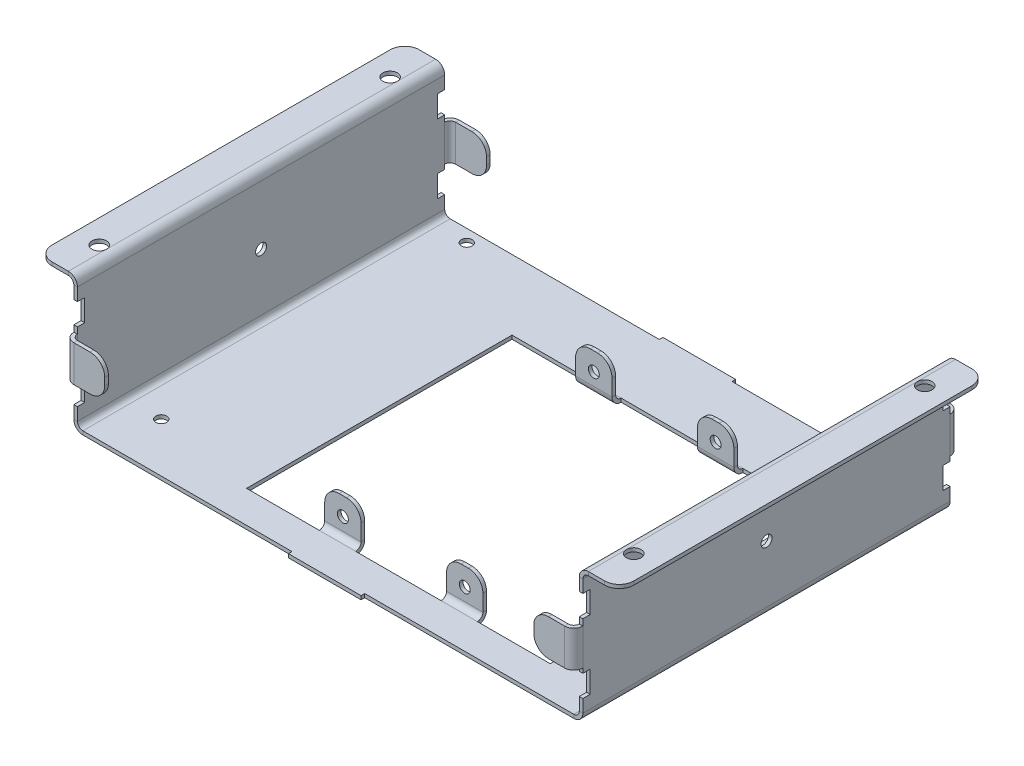
SolidWorks part; units mm, degrees
note: The reader was unsure of these and kept them because the rebuilt part matched: flange length of "Edge-Flange1", "Edge-Flange2", "Edge-Flange3", "Edge-Flange5", "Edge-Flange6".
material "Galvanized Steel"
ref_plane "Front Plane" through (0, 0, 0) normal (0, 0, 1) x (1, 0, 0)
ref_plane "Top Plane" through (0, 0, 0) normal (0, 1, 0) x (1, 0, 0)
ref_plane "Right Plane" through (0, 0, 0) normal (1, 0, 0) x (0, 0, -1)
sketch "Sketch2" plane through (0, 0, 0) normal (0, 1, 0) x (1, 0, 0)
  line L0 (-67.5, -45) -> (-10, -45)
  line L1 (10, 56) -> (67.5, 56)
  line L2 (67.5, -45) -> (67.5, 56)
  line L3 (10, -45) -> (67.5, -45)
  line L4 (-67.5, -45) -> (-67.5, 56)
  line L5 (10, 56) -> (10, 57)
  line L6 (10, 57) -> (-10, 57)
  line L7 (-31.3, 36.8) -> (52.2, 36.8)
  line L8 (-31.3, 36.8) -> (-31.3, -36.2)
  line L9 (-31.3, -36.2) -> (52.2, -36.2)
  line L10 (52.2, 36.8) -> (52.2, -36.2)
  line L11 (-10, 56) -> (-10, 57)
  line L13 (-10, -45) -> (-10, -46)
  line L14 (-10, -46) -> (10, -46)
  line L15 (-67.5, 56) -> (-10, 56)
  line L16 (10, -45) -> (10, -46)
  point P0 (0, 0)
  point P6 (-10, 56.5)
  point P19 (-10, -45.5)
  dimension "D1" = 101
  dimension "D2" = 45
  dimension "D3" = 135
  dimension "D4" = 83.5
  dimension "D5" = 36.2
  dimension "D6" = 73
  dimension "D7" = 67.5
  dimension "D8" = 8.8
  dimension "D9" = 57.5
  dimension "D10" = 20
  dimension "D11" = 1
  dimension "D12" = 1
  dimension "D13" = 20
  dimension "D14" = 57.5
base flange "Base-Flange1" sketch "Sketch2" thickness 1 reverse thickness direction no parameters "D1"=1
edge flange "Edge-Flange1" sketch "Sketch11" flange profiles "Sketch11", "Sketch12" flange angle 90 flange length 10 flange position bend outside bend radius 1.5 thickness 1 relief rectangular parameters "D6"=10, "D8"=1
sketch "Sketch11" plane through (0, 0, 36.2) normal (0, 0, -1) x (-1, 0, 0)
  line L2 (-32.2, 0) -> (-32.2, 6)
  line L3 (-28.2, 10) -> (-26.2, 10)
  line L4 (-22.2, 6) -> (-22.2, 0)
  line L5 (31.3, 0) -> (-52.2, 0) construction
  line L6 (-22.2, 0) -> (-32.2, 0)
  arc A0 (-32.2, 6) -> (-28.2, 10) centre (-28.2, 6) cw
  arc A1 (-26.2, 10) -> (-22.2, 6) centre (-26.2, 6) cw
  point P9 (-32.2, 10)
  point P12 (-22.2, 10)
  dimension "D4" = 4
  dimension "D1" = 20
  dimension "D2" = 10
  dimension "D3" = 10
sketch "Sketch12" plane through (0, 0, -36.8) normal (0, 0, 1) x (1, 0, 0)
  line L0 (52.2, 0) -> (-31.3, 0) construction
  line L1 (32.2, 0) -> (22.2, 0)
  line L2 (22.2, 0) -> (22.2, 6)
  line L3 (26.2, 10) -> (28.2, 10)
  line L4 (32.2, 6) -> (32.2, 0)
  arc A0 (22.2, 6) -> (26.2, 10) centre (26.2, 6) cw
  arc A1 (28.2, 10) -> (32.2, 6) centre (28.2, 6) cw
  point P9 (22.2, 10)
  point P12 (32.2, 10)
  dimension "D4" = 4
  dimension "D1" = 20
  dimension "D2" = 10
  dimension "D3" = 10
bend "EdgeBend1" bend radius 1.5 bend angle 90 parameters "D5"=1
bend "EdgeBend2" bend radius 1.5 bend angle 90 parameters "D5"=2
edge flange "Edge-Flange2" sketch "Sketch17" flange profiles "Sketch17", "Sketch18" flange angle 90 flange length 10 flange position bend outside bend radius 1.5 thickness 1 relief rectangular parameters "D6"=10, "D8"=1
sketch "Sketch17" plane through (0, 0, -36.8) normal (0, 0, 1) x (1, 0, 0)
  line L2 (-11.3, 0) -> (-11.3, 6)
  line L3 (-7.3, 10) -> (-5.3, 10)
  line L4 (-1.3, 6) -> (-1.3, 0)
  line L5 (22.2, 0) -> (-31.3, 0) construction
  line L6 (-1.3, 0) -> (-11.3, 0)
  arc A0 (-5.3, 10) -> (-1.3, 6) centre (-5.3, 6) cw
  arc A1 (-11.3, 6) -> (-7.3, 10) centre (-7.3, 6) cw
  point P9 (-1.3, 10)
  point P12 (-11.3, 10)
  dimension "D4" = 4
  dimension "D1" = 20
  dimension "D2" = 10
  dimension "D3" = 10
sketch "Sketch18" plane through (0, 0, 36.2) normal (0, 0, -1) x (-1, 0, 0)
  line L0 (31.3, 0) -> (-22.2, 0) construction
  line L1 (11.3, 0) -> (1.3, 0)
  line L2 (1.3, 0) -> (1.3, 6)
  line L3 (5.3, 10) -> (7.3, 10)
  line L4 (11.3, 6) -> (11.3, 0)
  arc A0 (1.3, 6) -> (5.3, 10) centre (5.3, 6) cw
  arc A1 (7.3, 10) -> (11.3, 6) centre (7.3, 6) cw
  point P9 (1.3, 10)
  point P12 (11.3, 10)
  dimension "D4" = 4
  dimension "D1" = 20
  dimension "D2" = 10
  dimension "D3" = 10
bend "EdgeBend3" bend radius 1.5 bend angle 90 parameters "D5"=3
bend "EdgeBend4" bend radius 1.5 bend angle 90 parameters "D5"=4
edge flange "Edge-Flange3" sketch "Sketch23" flange profiles "Sketch23", "Sketch24" flange angle 90 flange length 33.5 flange position bend outside bend radius 1.5 thickness 1 relief rectangular parameters "D6"=10, "D8"=1
sketch "Sketch23" plane through (-67.5, 0, 0) normal (-1, 0, 0) x (0, 0, 1)
  line L2 (-56, 0) -> (-56, 33.5)
  line L3 (-56, 33.5) -> (45, 33.5)
  line L4 (45, 33.5) -> (45, 0)
  line L5 (-56, 0) -> (45, 0) construction
  line L6 (-56, 0) -> (45, 0)
  dimension "D1" = 33.5
sketch "Sketch24" plane through (67.5, 0, 0) normal (1, 0, 0) x (0, 0, -1)
  line L0 (-45, 0) -> (56, 0) construction
  line L1 (-45, 0) -> (56, 0)
  line L2 (-45, 0) -> (-45, 33.5)
  line L3 (-45, 33.5) -> (56, 33.5)
  line L4 (56, 33.5) -> (56, 0)
  dimension "D1" = 33.5
bend "EdgeBend5" bend radius 1.5 bend angle 90 parameters "D5"=5
bend "EdgeBend6" bend radius 1.5 bend angle 90 parameters "D5"=6
edge flange "Edge-Flange5" sketch "Sketch32" flange profiles "Sketch32", "Sketch34", "Sketch36", "Sketch38" flange angle 90 flange length 10 flange position bend outside bend radius 1.5 thickness 1 relief rectangular parameters "D6"=10, "D8"=1
sketch "Sketch32" plane through (69, 0, 45) normal (0, 0, 1) x (0, 1, 0)
  line L0 (33.5, 0) -> (1.5, 0) construction
  line L1 (22.25, 0) -> (12.25, 0)
  line L2 (12.25, 0) -> (12.25, 6)
  line L3 (16.25, 10) -> (18.25, 10)
  line L4 (22.25, 6) -> (22.25, 0)
  line L5 (-1, 136.5) -> (-1, 79) construction
  arc A0 (18.25, 10) -> (22.25, 6) centre (18.25, 6) cw
  arc A1 (12.25, 6) -> (16.25, 10) centre (16.25, 6) cw
  point P10 (22.25, 10)
  point P13 (12.25, 10)
  dimension "D4" = 4
  dimension "D1" = 13.25
  dimension "D2" = 10
  dimension "D3" = 10
sketch "Sketch34" plane through (69, 0, -56) normal (0, 0, -1) x (0, -1, 0)
  line L0 (-1.5, 0) -> (-33.5, 0) construction
  line L1 (-12.25, 0) -> (-22.25, 0)
  line L2 (-22.25, 0) -> (-22.25, 6)
  line L3 (-18.25, 10) -> (-16.25, 10)
  line L4 (-12.25, 6) -> (-12.25, 0)
  line L7 (1, 79) -> (1, 136.5) construction
  arc A0 (-22.25, 6) -> (-18.25, 10) centre (-18.25, 6) cw
  arc A1 (-16.25, 10) -> (-12.25, 6) centre (-16.25, 6) cw
  point P9 (-22.25, 10)
  point P12 (-12.25, 10)
  dimension "D4" = 4
  dimension "D1" = 13.25
  dimension "D2" = 10
  dimension "D3" = 10
sketch "Sketch36" plane through (-69, 0, 45) normal (0, 0, 1) x (0, -1, 0)
  line L0 (-1.5, 0) -> (-33.5, 0) construction
  line L1 (-12.25, 0) -> (-22.25, 0)
  line L2 (-22.25, 0) -> (-22.25, 6)
  line L3 (-18.25, 10) -> (-16.25, 10)
  line L4 (-12.25, 6) -> (-12.25, 0)
  line L5 (1, 1.5) -> (1, 59) construction
  arc A0 (-16.25, 10) -> (-12.25, 6) centre (-16.25, 6) cw
  arc A1 (-22.25, 6) -> (-18.25, 10) centre (-18.25, 6) cw
  point P10 (-12.25, 10)
  point P13 (-22.25, 10)
  dimension "D4" = 4
  dimension "D1" = 13.25
  dimension "D2" = 10
  dimension "D3" = 10
sketch "Sketch38" plane through (-69, 0, -56) normal (0, 0, -1) x (0, 1, 0)
  line L0 (33.5, 0) -> (1.5, 0) construction
  line L1 (22.25, 0) -> (12.25, 0)
  line L2 (12.25, 0) -> (12.25, 6)
  line L3 (16.25, 10) -> (18.25, 10)
  line L4 (22.25, 6) -> (22.25, 0)
  line L5 (-1, 59) -> (-1, 1.5) construction
  arc A0 (18.25, 10) -> (22.25, 6) centre (18.25, 6) cw
  arc A1 (12.25, 6) -> (16.25, 10) centre (16.25, 6) cw
  point P10 (22.25, 10)
  point P13 (12.25, 10)
  dimension "D4" = 4
  dimension "D1" = 13.25
  dimension "D2" = 10
  dimension "D3" = 10
bend "EdgeBend9" bend radius 1.5 bend angle 90 parameters "D5"=7
bend "EdgeBend10" bend radius 1.5 bend angle 90 parameters "D5"=9
bend "EdgeBend11" bend radius 1.5 bend angle 90 parameters "D5"=10
bend "EdgeBend12" bend radius 1.5 bend angle 90 parameters "D5"=11
edge flange "Edge-Flange6" sketch "Sketch43" flange profiles "Sketch43", "Sketch44" flange angle 90 flange length 10 flange position bend outside bend radius 1.5 thickness 1 relief rectangular parameters "D6"=10, "D8"=1
sketch "Sketch43" plane through (70, 33.5, 0) normal (0, -1, 0) x (0, 0, -1)
  line L2 (-45, 0) -> (-45, 6)
  line L3 (-41, 10) -> (52, 10)
  line L4 (56, 6) -> (56, 0)
  line L6 (56, 0) -> (-45, 0) construction
  line L7 (56, 0) -> (-45, 0)
  arc A0 (-45, 6) -> (-41, 10) centre (-41, 6) cw
  arc A1 (52, 10) -> (56, 6) centre (52, 6) cw
  dimension "D1" = 4
sketch "Sketch44" plane through (-70, 33.5, 0) normal (0, -1, 0) x (0, 0, 1)
  line L0 (45, 0) -> (-56, 0) construction
  line L1 (45, 0) -> (-56, 0)
  line L2 (45, 0) -> (45, 6)
  line L3 (41, 10) -> (-52, 10)
  line L4 (-56, 6) -> (-56, 0)
  arc A0 (-52, 10) -> (-56, 6) centre (-52, 6) ccw
  arc A1 (45, 6) -> (41, 10) centre (41, 6) ccw
  dimension "D1" = 4
bend "EdgeBend13" bend radius 1.5 bend angle 90 parameters "D5"=12
bend "EdgeBend14" bend radius 1.5 bend angle 90 parameters "D5"=13
sketch "Sketch45" plane through (0, 36, 0) normal (0, 1, 0) x (1, 0, 0)
  line L0 (-80, 5.5) -> (-69, 5.5) construction
  line L1 (-80, -41) -> (-80, 52) construction
  line L2 (-69, 56) -> (-69, -45) construction
  line L3 (69, 5.5) -> (80, 5.5) construction
  line L4 (69, -45) -> (69, 56) construction
  line L5 (80, 52) -> (80, -41) construction
  point P6 (-73.5, 45.5)
  point P7 (-73.5, -34.5)
  point P14 (73.5, 45.5)
  point P15 (73.5, -34.5)
  dimension "D1" = 40
  dimension "D2" = 40
  dimension "D3" = 40
  dimension "D4" = 40
hole_wizard "Ø4.0mm Dowel Hole1" positions "Sketch46" profile "Sketch48" hole size "Ø4.0" standard "ANSI Metric" end condition up to next
sketch "Sketch46" plane through (0, 36, 0) normal (0, 1, 0) x (1, 0, 0)
  point P0 (-73.5, 45.5)
  point P3 (-73.5, -34.5)
  point P6 (73.5, -34.5)
  point P9 (73.5, 45.5)
sketch "Sketch48" plane through (-73.5, 36, -45.5) normal (1, 0, 0) x (0, 0, 1)
  line L0 (0, 0) -> (0, 1)
  line L1 (0, 1) -> (2, 1)
  line L2 (2, 1) -> (2, 0)
  line L5 (2, 0) -> (0, 0)
  line L11 (0, -6.35) -> (0, 107.95) construction
  dimension "Thru Hole Dia." = 4
  dimension "Thru Hole Depth" = 1
sketch "Sketch50" plane through (-70, 0, 0) normal (-1, 0, 0) x (0, 0, 1)
  line L0 (-56, 33.5) -> (-56, 22.25) construction
  line L1 (-56, 30) -> (-54, 30)
  line L2 (-56, 30) -> (-56, 24)
  line L3 (-56, 24) -> (-54, 24)
  line L4 (-54, 30) -> (-54, 24)
  line L6 (-56, 36) -> (-45.5, 36) construction
  line L7 (-56, 12.25) -> (-56, 1.5) construction
  line L8 (-56, 11) -> (-54, 11)
  line L9 (-56, 11) -> (-56, 5)
  line L10 (-56, 5) -> (-54, 5)
  line L11 (-54, 11) -> (-54, 5)
  line L12 (-56, -1) -> (45, -1) construction
  line L13 (-5.5, 33.5) -> (-5.5, 1.5) construction
  line L14 (45, 33.5) -> (-56, 33.5) construction
  line L15 (45, 1.5) -> (-56, 1.5) construction
  line L16 (43, 11) -> (43, 5)
  line L17 (45, 5) -> (43, 5)
  line L18 (45, 11) -> (45, 5)
  line L19 (45, 11) -> (43, 11)
  line L20 (43, 30) -> (43, 24)
  line L21 (45, 24) -> (43, 24)
  line L22 (45, 30) -> (45, 24)
  line L23 (45, 30) -> (43, 30)
  point P6 (-55, 30)
  dimension "D1" = 2
  dimension "D2" = 6
  dimension "D3" = 6
  dimension "D4" = 2
  dimension "D5" = 6
  dimension "D6" = 6
extrude "Cut-Extrude1" cut sketch "Sketch50" against normal blind 143 normal cut yes
unfold "Unfold1" [suppressed]
sketch "Sketch45-2" [suppressed] plane through (34.427, 0, 0) normal (0, 1, 0) x (1, 0, 0)
  line L0 (-79, 5.5) -> (-68, 5.5) construction
  line L3 (68, 5.5) -> (79, 5.5) construction
  point P6 (-73.5, 45.5)
  point P7 (-73.5, -34.5)
  point P14 (73.5, 45.5)
  point P15 (73.5, -34.5)
  dimension "D1" = 40
  dimension "D2" = 40
  dimension "D3" = 40
  dimension "D4" = 40
sketch "Sketch50-1" plane through (-68.5708, -1, 0) normal (0, -1, 0) x (0, 0, 1)
  line L1 (-56, 29.5) -> (-54, 29.5)
  line L2 (-56, 29.5) -> (-56, 23.5)
  line L3 (-56, 23.5) -> (-54, 23.5)
  line L4 (-54, 29.5) -> (-54, 23.5)
  line L8 (-56, 11) -> (-54, 11)
  line L9 (-56, 11) -> (-56, 5)
  line L10 (-56, 5) -> (-54, 5)
  line L11 (-54, 11) -> (-54, 5)
  line L12 (-56, -1.0708) -> (45, -1.0708) construction
  line L13 (-5.5, 33.5) -> (-5.5, 0.5) construction
  line L16 (43, 11) -> (43, 5)
  line L17 (45, 5) -> (43, 5)
  line L18 (45, 11) -> (45, 5)
  line L19 (45, 11) -> (43, 11)
  line L20 (43, 29.5) -> (43, 23.5)
  line L21 (45, 23.5) -> (43, 23.5)
  line L22 (45, 29.5) -> (45, 23.5)
  line L23 (45, 29.5) -> (43, 29.5)
  dimension "D1" = 2
  dimension "D2" = 6
  dimension "D4" = 2
  dimension "D5" = 6
  dimension "D6" = 6.0708
sketch "Sketch51" plane through (70, 0, 0) normal (1, 0, 0) x (0, 0, -1)
  line L0 (-31.4511, 24.5488) -> (-31.4511, 22.9482) construction
  line L1 (55.5489, 22.9482) -> (-34.4511, 22.9482) construction
  line L3 (52.5489, 24.5488) -> (52.5498, 22.935) construction
  point P0 (-31.4511, 24.5488)
sketch "Sketch53" plane through (0, 0, 0) normal (0, 1, 0) x (1, 0, 0)
  point P0 (-59.4974, 52.5489)
  point P1 (59.5026, 52.5489)
  point P3 (-59.4974, -31.4511)
  point P5 (59.5026, -31.4511)
hole_wizard "Ø3.0mm Dowel Hole1" positions "Sketch56" profile "Sketch57" hole size "Ø3.0" standard "ANSI Metric" end condition up to next
sketch "Sketch56" plane through (0, 0, 0) normal (0, 1, 0) x (1, 0, 0)
  point P0 (-59.4974, 52.5489)
  point P3 (59.5026, 52.5489)
  point P6 (-59.4974, -31.4511)
  point P9 (59.5026, -31.4511)
sketch "Sketch57" plane through (-59.4974, 0, -52.5489) normal (1, 0, 0) x (0, 0, 1)
  line L0 (0, 0) -> (0, 1)
  line L1 (0, 1) -> (1.5, 1)
  line L2 (1.5, 1) -> (1.5, 0)
  line L5 (1.5, 0) -> (0, 0)
  line L11 (0, -6.35) -> (0, 107.95) construction
  dimension "Thru Hole Dia." = 3
  dimension "Thru Hole Depth" = 1
sketch "Sketch58" plane through (0, 0, 34.7) normal (0, 0, 1) x (1, 0, 0)
  line L1 (-1.3, 6) -> (-1.3, 1.5) construction
  line L2 (-67.5, 0) -> (-10, 0) construction
  line L3 (10, 0) -> (67.5, 0) construction
  line L4 (32.2, 6) -> (32.2, 1.5) construction
  point P0 (-6.3, 5)
  point P6 (27.2, 5)
  point P11 (32.2, 3.75)
  dimension "D1" = 5
  dimension "D2" = 5
  dimension "D3" = 5
  dimension "D4" = 5
sketch "Sketch59" plane through (0, 0, -35.3) normal (0, 0, -1) x (-1, 0, 0)
  point P0 (-27.2, 5)
  point P1 (6.3, 5)
hole_wizard "Ø3.0mm Dowel Hole2" positions "Sketch60" profile "Sketch61" hole size "Ø3.0" standard "ANSI Metric" end condition up to next
sketch "Sketch60" plane through (0, 0, -35.3) normal (0, 0, -1) x (-1, 0, 0)
  point P0 (-27.2, 5)
  point P3 (6.3, 5)
  point P6 (6.3, 5)
sketch "Sketch61" plane through (27.2, 5, -35.3) normal (1, 0, 0) x (0, 1, 0)
  line L0 (0, 0) -> (0, 1)
  line L1 (0, 1) -> (1.5, 1)
  line L2 (1.5, 1) -> (1.5, 0)
  line L5 (1.5, 0) -> (0, 0)
  line L11 (0, -6.35) -> (0, 107.95) construction
  dimension "Thru Hole Dia." = 3
  dimension "Thru Hole Depth" = 1
hole_wizard "Ø3.0mm Dowel Hole3" positions "Sketch64" profile "Sketch65" hole size "Ø3.0" standard "ANSI Metric" end condition up to next
sketch "Sketch64" plane through (0, 0, 34.7) normal (0, 0, 1) x (1, 0, 0)
  point P0 (-6.3, 5)
  point P3 (27.2, 5)
sketch "Sketch65" plane through (-6.3, 5, 34.7) normal (1, 0, 0) x (0, -1, 0)
  line L0 (0, 0) -> (0, 1)
  line L1 (0, 1) -> (1.5, 1)
  line L2 (1.5, 1) -> (1.5, 0)
  line L5 (1.5, 0) -> (0, 0)
  line L11 (0, -6.35) -> (0, 107.95) construction
  dimension "Thru Hole Dia." = 3
  dimension "Thru Hole Depth" = 1
ref_plane "Plane1" through (0, 0, 0) normal (-1, 0, 0) x (0, 0, 1)
sketch "Sketch66" plane through (70, 0, 0) normal (1, 0, 0) x (0, 0, -1)
  line L0 (-45, 17.25) -> (56, 17.25) construction
  line L1 (-45, 22.25) -> (-45, 12.25) construction
  line L2 (56, 12.25) -> (56, 22.25) construction
  point P6 (5.5, 17.25)
hole_wizard "Ø3.0 (3) Diameter Hole1" positions "Sketch67" profile "Sketch68" hole size "Ø3.0" standard "ANSI Metric" end condition up to next
sketch "Sketch67" plane through (70, 0, 0) normal (1, 0, 0) x (0, 0, -1)
  point P0 (5.5, 17.25)
sketch "Sketch68" plane through (70, 17.25, -5.5) normal (0, 1, 0) x (0, 0, -1)
  line L0 (0, 0) -> (0, 1)
  line L1 (0, 1) -> (1.5, 1)
  line L2 (1.5, 1) -> (1.5, 0)
  line L5 (1.5, 0) -> (0, 0)
  line L11 (0, -6.35) -> (0, 107.95) construction
  dimension "Thru Hole Dia." = 3
  dimension "Thru Hole Depth" = 1
sketch "Sketch70" plane through (-70, 0, 0) normal (-1, 0, 0) x (0, 0, 1)
  line L0 (-56, 17.25) -> (45, 17.25) construction
  line L1 (-56, 22.25) -> (-56, 12.25) construction
  line L2 (45, 12.25) -> (45, 22.25) construction
  point P6 (-5.5, 17.25)
hole_wizard "Ø3.0mm Dowel Hole4" positions "Sketch71" profile "Sketch72" hole size "Ø3.0" standard "ANSI Metric" end condition up to next
sketch "Sketch71" plane through (-70, 0, 0) normal (-1, 0, 0) x (0, 0, 1)
  point P0 (-5.5, 17.25)
sketch "Sketch72" plane through (-70, 17.25, -5.5) normal (0, 1, 0) x (0, 0, 1)
  line L0 (0, 0) -> (0, 1)
  line L1 (0, 1) -> (1.5, 1)
  line L2 (1.5, 1) -> (1.5, 0)
  line L5 (1.5, 0) -> (0, 0)
  line L11 (0, -6.35) -> (0, 107.95) construction
  dimension "Thru Hole Dia." = 3
  dimension "Thru Hole Depth" = 1
sketch "Bend-Lines1" [suppressed] plane through (0, 0, 0) normal (0, 1, 0) x (1, 0, 0)
sketch "Bounding-Box1" [suppressed] plane through (0, 0, 0) normal (0, 1, 0) x (1, 0, 0)
sheet metal parameters "Sheet-Metal1" thickness 1 parameters "D1"=1
flat pattern "Flat-Pattern1"
sketch "Bend-Lines2" plane through (0, 0, 0) normal (0, 1, 0) x (1, 0, 0)
sketch3d "Bounding-Box2" [suppressed]
  line L0 (67.5, -54, 0) -> (-67.5, -54, 0) construction
  line L1 (67.5, 54, 0) -> (-67.5, 54, 0) construction
  line L2 (67.5, -54, 0) -> (67.5, 54, 0) construction
  line L3 (-67.5, -54, 0) -> (-67.5, 54, 0) construction
sheet metal parameters "Sheet-Metal2" thickness 1 parameters "D1"=1
flat pattern "Flat-Pattern1"
sketch "Bend-Lines2" plane through (0, 0, 0) normal (0, 1, 0) x (1, 0, 0)
  line L0 (22.2, 35.0146) -> (32.2, 35.0146) construction
  line L1 (32.2, -35.4146) -> (22.2, -35.4146) construction
  line L2 (22.2, 35.0146) -> (32.2, 35.0146) construction
  line L3 (32.2, -35.4146) -> (22.2, -35.4146) construction
sketch3d "Bounding-Box2" [suppressed]
  line L0 (67.5, -45, 0) -> (-67.5, -45, 0) construction
  line L1 (67.5, 56, 0) -> (-67.5, 56, 0) construction
  line L2 (67.5, -45, 0) -> (67.5, 56, 0) construction
  line L3 (-67.5, -45, 0) -> (-67.5, 56, 0) construction
bend of the flat pattern "Flatten-<EdgeBend1>1"
bend of the flat pattern "Flatten-<EdgeBend2>1"
sheet metal parameters "Sheet-Metal3" thickness 1 parameters "D1"=1
flat pattern "Flat-Pattern1"
sketch "Bend-Lines2" plane through (0, 0, 0) normal (0, 1, 0) x (1, 0, 0)
  line L0 (22.2, 35.0146) -> (32.2, 35.0146) construction
  line L1 (32.2, -35.4146) -> (22.2, -35.4146) construction
  line L2 (22.2, 35.0146) -> (32.2, 35.0146) construction
  line L3 (32.2, -35.4146) -> (22.2, -35.4146) construction
  line L4 (22.2, -35.4146) -> (-11.3, -35.4146) construction
  line L5 (-11.3, 35.0146) -> (22.2, 35.0146) construction
  line L6 (22.2, -35.4146) -> (-11.3, -35.4146) construction
  line L7 (-11.3, 35.0146) -> (22.2, 35.0146) construction
sketch3d "Bounding-Box2" [suppressed]
  line L0 (67.5, -45, 0) -> (-67.5, -45, 0) construction
  line L1 (67.5, 56, 0) -> (-67.5, 56, 0) construction
  line L2 (67.5, -45, 0) -> (67.5, 56, 0) construction
  line L3 (-67.5, -45, 0) -> (-67.5, 56, 0) construction
bend of the flat pattern "Flatten-<EdgeBend1>1"
bend of the flat pattern "Flatten-<EdgeBend2>1"
bend of the flat pattern "Flatten-<EdgeBend3>1"
bend of the flat pattern "Flatten-<EdgeBend4>1"
sheet metal parameters "Sheet-Metal4" thickness 1 parameters "D1"=1
flat pattern "Flat-Pattern1"
sketch "Bend-Lines2" plane through (0, 0, 0) normal (0, 1, 0) x (1, 0, 0)
  line L0 (22.2, 35.0146) -> (32.2, 35.0146) construction
  line L1 (32.2, -35.4146) -> (22.2, -35.4146) construction
  line L2 (22.2, 35.0146) -> (32.2, 35.0146) construction
  line L3 (32.2, -35.4146) -> (22.2, -35.4146) construction
  line L4 (22.2, -35.4146) -> (-11.3, -35.4146) construction
  line L5 (-11.3, 35.0146) -> (22.2, 35.0146) construction
  line L6 (22.2, -35.4146) -> (-11.3, -35.4146) construction
  line L7 (-11.3, 35.0146) -> (22.2, 35.0146) construction
  line L8 (68.2854, -45) -> (68.2854, 56) construction
  line L9 (-68.2854, 56) -> (-68.2854, -45) construction
  line L10 (68.2854, -45) -> (68.2854, 56) construction
  line L11 (-68.2854, 56) -> (-68.2854, -45) construction
sketch3d "Bounding-Box2" [suppressed]
  line L0 (104.0708, -45, 0) -> (-104.0708, -45, 0) construction
  line L1 (104.0708, 56, 0) -> (-104.0708, 56, 0) construction
  line L2 (104.0708, -45, 0) -> (104.0708, 56, 0) construction
  line L3 (-104.0708, -45, 0) -> (-104.0708, 56, 0) construction
bend of the flat pattern "Flatten-<EdgeBend1>1"
bend of the flat pattern "Flatten-<EdgeBend2>1"
bend of the flat pattern "Flatten-<EdgeBend3>1"
bend of the flat pattern "Flatten-<EdgeBend4>1"
bend of the flat pattern "Flatten-<EdgeBend5>1"
bend of the flat pattern "Flatten-<EdgeBend6>1"
sheet metal parameters "Sheet-Metal6" thickness 1 parameters "D1"=1
flat pattern "Flat-Pattern1"
sketch "Bend-Lines2" plane through (0, 0, 0) normal (0, 1, 0) x (1, 0, 0)
  line L0 (22.2, 35.0146) -> (32.2, 35.0146) construction
  line L1 (32.2, -35.4146) -> (22.2, -35.4146) construction
  line L2 (22.2, 35.0146) -> (32.2, 35.0146) construction
  line L3 (32.2, -35.4146) -> (22.2, -35.4146) construction
  line L4 (22.2, -35.4146) -> (-11.3, -35.4146) construction
  line L5 (-11.3, 35.0146) -> (22.2, 35.0146) construction
  line L6 (22.2, -35.4146) -> (-11.3, -35.4146) construction
  line L7 (-11.3, 35.0146) -> (22.2, 35.0146) construction
  line L8 (68.2854, -45) -> (68.2854, 56) construction
  line L9 (-68.2854, 56) -> (-68.2854, -45) construction
  line L10 (68.2854, -45) -> (68.2854, 56) construction
  line L11 (-68.2854, 56) -> (-68.2854, -45) construction
  line L12 (80.8208, -46.1781) -> (90.8208, -46.1781) construction
  line L13 (80.8208, -46.1781) -> (90.8208, -46.1781) construction
  line L14 (-80.8208, 57.1781) -> (-90.8208, 57.1781) construction
  line L15 (-90.8208, -46.1781) -> (-80.8208, -46.1781) construction
  line L16 (90.8208, 57.1781) -> (80.8208, 57.1781) construction
  line L17 (-80.8208, 57.1781) -> (-90.8208, 57.1781) construction
  line L18 (-90.8208, -46.1781) -> (-80.8208, -46.1781) construction
  line L19 (90.8208, 57.1781) -> (80.8208, 57.1781) construction
sketch3d "Bounding-Box2" [suppressed]
  line L0 (-104.0708, -56.356, 0) -> (104.0708, -56.3562, 0) construction
  line L1 (-104.0707, 67.3562, 0) -> (104.0709, 67.356, 0) construction
  line L2 (-104.0708, -56.356, 0) -> (-104.0707, 67.3562, 0) construction
  line L3 (104.0708, -56.3562, 0) -> (104.0709, 67.356, 0) construction
bend of the flat pattern "Flatten-<EdgeBend1>1"
bend of the flat pattern "Flatten-<EdgeBend2>1"
bend of the flat pattern "Flatten-<EdgeBend3>1"
bend of the flat pattern "Flatten-<EdgeBend4>1"
bend of the flat pattern "Flatten-<EdgeBend5>1"
bend of the flat pattern "Flatten-<EdgeBend6>1"
bend of the flat pattern "Flatten-<EdgeBend9>1"
bend of the flat pattern "Flatten-<EdgeBend10>1"
bend of the flat pattern "Flatten-<EdgeBend11>1"
bend of the flat pattern "Flatten-<EdgeBend12>1"
sheet metal parameters "Sheet-Metal7" thickness 1 parameters "D1"=1
flat pattern "Flat-Pattern1"
sketch "Bend-Lines2" plane through (0, 0, 0) normal (0, 1, 0) x (1, 0, 0)
  line L0 (22.2, 35.0146) -> (32.2, 35.0146) construction
  line L1 (32.2, -35.4146) -> (22.2, -35.4146) construction
  line L2 (22.2, 35.0146) -> (32.2, 35.0146) construction
  line L3 (32.2, -35.4146) -> (22.2, -35.4146) construction
  line L4 (22.2, -35.4146) -> (-11.3, -35.4146) construction
  line L5 (-11.3, 35.0146) -> (22.2, 35.0146) construction
  line L6 (22.2, -35.4146) -> (-11.3, -35.4146) construction
  line L7 (-11.3, 35.0146) -> (22.2, 35.0146) construction
  line L8 (68.2854, -45) -> (68.2854, 56) construction
  line L9 (-68.2854, 56) -> (-68.2854, -45) construction
  line L10 (68.2854, -45) -> (68.2854, 56) construction
  line L11 (-68.2854, 56) -> (-68.2854, -45) construction
  line L12 (80.8208, -46.1781) -> (90.8208, -46.1781) construction
  line L13 (80.8208, -46.1781) -> (90.8208, -46.1781) construction
  line L14 (-80.8208, 57.1781) -> (-90.8208, 57.1781) construction
  line L15 (-90.8208, -46.1781) -> (-80.8208, -46.1781) construction
  line L16 (90.8208, 57.1781) -> (80.8208, 57.1781) construction
  line L17 (-80.8208, 57.1781) -> (-90.8208, 57.1781) construction
  line L18 (-90.8208, -46.1781) -> (-80.8208, -46.1781) construction
  line L19 (90.8208, 57.1781) -> (80.8208, 57.1781) construction
  line L20 (-105.2489, 56) -> (-105.2489, -45) construction
  line L21 (105.2489, -45) -> (105.2489, 56) construction
  line L22 (-105.2489, 56) -> (-105.2489, -45) construction
  line L23 (105.2489, -45) -> (105.2489, 56) construction
sketch3d "Bounding-Box2" [suppressed]
  line L0 (-115.427, -56.356, 0) -> (115.427, -56.3562, 0) construction
  line L1 (-115.4269, 67.3562, 0) -> (115.4271, 67.356, 0) construction
  line L2 (-115.427, -56.356, 0) -> (-115.4269, 67.3562, 0) construction
  line L3 (115.427, -56.3562, 0) -> (115.4271, 67.356, 0) construction
bend of the flat pattern "Flatten-<EdgeBend1>1"
bend of the flat pattern "Flatten-<EdgeBend2>1"
bend of the flat pattern "Flatten-<EdgeBend3>1"
bend of the flat pattern "Flatten-<EdgeBend4>1"
bend of the flat pattern "Flatten-<EdgeBend5>1"
bend of the flat pattern "Flatten-<EdgeBend6>1"
bend of the flat pattern "Flatten-<EdgeBend9>1"
bend of the flat pattern "Flatten-<EdgeBend10>1"
bend of the flat pattern "Flatten-<EdgeBend11>1"
bend of the flat pattern "Flatten-<EdgeBend12>1"
bend of the flat pattern "Flatten-<EdgeBend13>1"
bend of the flat pattern "Flatten-<EdgeBend14>1"
sheet metal parameters "Sheet-Metal8" thickness 1 parameters "D1"=1
flat pattern "Flat-Pattern1" [suppressed]
sketch "Bend-Lines2" plane through (0, 0, 0) normal (0, 1, 0) x (1, 0, 0)
  line L0 (22.2, 35.0146) -> (32.2, 35.0146) construction
  line L1 (32.2, -35.4146) -> (22.2, -35.4146) construction
  line L2 (22.2, 35.0146) -> (32.2, 35.0146) construction
  line L3 (32.2, -35.4146) -> (22.2, -35.4146) construction
  line L4 (22.2, -35.4146) -> (-11.3, -35.4146) construction
  line L5 (-11.3, 35.0146) -> (22.2, 35.0146) construction
  line L6 (22.2, -35.4146) -> (-11.3, -35.4146) construction
  line L7 (-11.3, 35.0146) -> (22.2, 35.0146) construction
  line L8 (68.2854, -45) -> (68.2854, 56) construction
  line L9 (-68.2854, 56) -> (-68.2854, -45) construction
  line L10 (68.2854, -45) -> (68.2854, 56) construction
  line L11 (-68.2854, 56) -> (-68.2854, -45) construction
  line L12 (80.8208, -46.1781) -> (90.8208, -46.1781) construction
  line L13 (80.8208, -46.1781) -> (90.8208, -46.1781) construction
  line L14 (-80.8208, 57.1781) -> (-90.8208, 57.1781) construction
  line L15 (-90.8208, -46.1781) -> (-80.8208, -46.1781) construction
  line L16 (90.8208, 57.1781) -> (80.8208, 57.1781) construction
  line L17 (-80.8208, 57.1781) -> (-90.8208, 57.1781) construction
  line L18 (-90.8208, -46.1781) -> (-80.8208, -46.1781) construction
  line L19 (90.8208, 57.1781) -> (80.8208, 57.1781) construction
  line L20 (-103.2489, 56) -> (-103.2489, -45) construction
  line L21 (103.2489, -45) -> (103.2489, 56) construction
  line L22 (-103.2489, 56) -> (-103.2489, -45) construction
  line L23 (103.2489, -45) -> (103.2489, 56) construction
sketch3d "Bounding-Box2" [suppressed]
  line L0 (-113.427, -56.356, 0) -> (113.427, -56.3562, 0) construction
  line L1 (-113.4269, 67.3562, 0) -> (113.4271, 67.356, 0) construction
  line L2 (-113.427, -56.356, 0) -> (-113.4269, 67.3562, 0) construction
  line L3 (113.427, -56.3562, 0) -> (113.4271, 67.356, 0) construction
bend of the flat pattern "Flatten-<EdgeBend1>1"
bend of the flat pattern "Flatten-<EdgeBend2>1"
bend of the flat pattern "Flatten-<EdgeBend3>1"
bend of the flat pattern "Flatten-<EdgeBend4>1"
bend of the flat pattern "Flatten-<EdgeBend5>1"
bend of the flat pattern "Flatten-<EdgeBend6>1"
bend of the flat pattern "Flatten-<EdgeBend9>1"
bend of the flat pattern "Flatten-<EdgeBend10>1"
bend of the flat pattern "Flatten-<EdgeBend11>1"
bend of the flat pattern "Flatten-<EdgeBend12>1"
bend of the flat pattern "Flatten-<EdgeBend13>1"
bend of the flat pattern "Flatten-<EdgeBend14>1"
sketch "Sketch45-1" [suppressed] plane through (34.427, 0, 0) normal (0, 1, 0) x (1, 0, 0)
  line L0 (-79, 5.5) -> (-68, 5.5) construction
  line L3 (68, 5.5) -> (79, 5.5) construction
  point P6 (-73.5, 45.5)
  point P7 (-73.5, -34.5)
  point P14 (73.5, 45.5)
  point P15 (73.5, -34.5)
  dimension "D1" = 40
  dimension "D2" = 40
  dimension "D3" = 40
  dimension "D4" = 40
sheet metal parameters "Sheet-Metal9" thickness 1 parameters "D1"=1
flat pattern "Flat-Pattern1" [suppressed]
sketch "Bend-Lines2" plane through (0, 0, 0) normal (0, 1, 0) x (1, 0, 0)
  line L0 (22.2, 35.0146) -> (32.2, 35.0146) construction
  line L1 (32.2, -35.4146) -> (22.2, -35.4146) construction
  line L2 (22.2, 35.0146) -> (32.2, 35.0146) construction
  line L3 (32.2, -35.4146) -> (22.2, -35.4146) construction
  line L4 (22.2, -35.4146) -> (-11.3, -35.4146) construction
  line L5 (-11.3, 35.0146) -> (22.2, 35.0146) construction
  line L6 (22.2, -35.4146) -> (-11.3, -35.4146) construction
  line L7 (-11.3, 35.0146) -> (22.2, 35.0146) construction
  line L8 (68.2854, -45) -> (68.2854, 56) construction
  line L9 (-68.2854, 56) -> (-68.2854, -45) construction
  line L10 (68.2854, -45) -> (68.2854, 56) construction
  line L11 (-68.2854, 56) -> (-68.2854, -45) construction
  line L12 (80.8208, -46.1781) -> (90.8208, -46.1781) construction
  line L13 (80.8208, -46.1781) -> (90.8208, -46.1781) construction
  line L14 (-80.8208, 57.1781) -> (-90.8208, 57.1781) construction
  line L15 (-90.8208, -46.1781) -> (-80.8208, -46.1781) construction
  line L16 (90.8208, 57.1781) -> (80.8208, 57.1781) construction
  line L17 (-80.8208, 57.1781) -> (-90.8208, 57.1781) construction
  line L18 (-90.8208, -46.1781) -> (-80.8208, -46.1781) construction
  line L19 (90.8208, 57.1781) -> (80.8208, 57.1781) construction
  line L20 (-103.2489, 56) -> (-103.2489, -45) construction
  line L21 (103.2489, -45) -> (103.2489, 56) construction
  line L22 (-103.2489, 56) -> (-103.2489, -45) construction
  line L23 (103.2489, -45) -> (103.2489, 56) construction
sketch3d "Bounding-Box2" [suppressed]
  line L0 (-113.427, -56.356, 0) -> (113.427, -56.3562, 0) construction
  line L1 (-113.4269, 67.3562, 0) -> (113.4271, 67.356, 0) construction
  line L2 (-113.427, -56.356, 0) -> (-113.4269, 67.3562, 0) construction
  line L3 (113.427, -56.3562, 0) -> (113.4271, 67.356, 0) construction
bend of the flat pattern "Flatten-<EdgeBend1>1"
bend of the flat pattern "Flatten-<EdgeBend2>1"
bend of the flat pattern "Flatten-<EdgeBend3>1"
bend of the flat pattern "Flatten-<EdgeBend4>1"
bend of the flat pattern "Flatten-<EdgeBend5>1"
bend of the flat pattern "Flatten-<EdgeBend6>1"
bend of the flat pattern "Flatten-<EdgeBend9>1"
bend of the flat pattern "Flatten-<EdgeBend10>1"
bend of the flat pattern "Flatten-<EdgeBend11>1"
bend of the flat pattern "Flatten-<EdgeBend12>1"
bend of the flat pattern "Flatten-<EdgeBend13>1"
bend of the flat pattern "Flatten-<EdgeBend14>1"
sketch "Sketch45-7" plane through (34.427, 0, 0) normal (0, 1, 0) x (1, 0, 0)
  line L0 (-79, 5.5) -> (-68, 5.5) construction
  line L3 (68, 5.5) -> (79, 5.5) construction
  point P6 (-73.5, 45.5)
  point P7 (-73.5, -34.5)
  point P14 (73.5, 45.5)
  point P15 (73.5, -34.5)
  dimension "D1" = 40
  dimension "D2" = 40
  dimension "D3" = 40
  dimension "D4" = 40
sketch "Sketch51-1" [suppressed] plane through (68.5708, -1, 0) normal (0, -1, 0) x (0, 0, -1)
  line L0 (-32.4511, 24.5488) -> (-32.4511, 22.9482) construction
  line L3 (51.5489, 24.5488) -> (51.5498, 22.935) construction
  point P0 (-32.4511, 24.5488)
sheet metal parameters "Sheet-Metal10" thickness 1 parameters "D1"=1
flat pattern "Flat-Pattern1" [suppressed]
sketch "Bend-Lines2" plane through (0, 0, 0) normal (0, 1, 0) x (1, 0, 0)
  line L0 (22.2, 35.0146) -> (32.2, 35.0146) construction
  line L1 (32.2, -35.4146) -> (22.2, -35.4146) construction
  line L2 (22.2, 35.0146) -> (32.2, 35.0146) construction
  line L3 (32.2, -35.4146) -> (22.2, -35.4146) construction
  line L4 (22.2, -35.4146) -> (-11.3, -35.4146) construction
  line L5 (-11.3, 35.0146) -> (22.2, 35.0146) construction
  line L6 (22.2, -35.4146) -> (-11.3, -35.4146) construction
  line L7 (-11.3, 35.0146) -> (22.2, 35.0146) construction
  line L8 (68.2854, -45) -> (68.2854, 56) construction
  line L9 (-68.2854, 56) -> (-68.2854, -45) construction
  line L10 (68.2854, -45) -> (68.2854, 56) construction
  line L11 (-68.2854, 56) -> (-68.2854, -45) construction
  line L12 (80.8208, -46.1781) -> (90.8208, -46.1781) construction
  line L13 (80.8208, -46.1781) -> (90.8208, -46.1781) construction
  line L14 (-80.8208, 57.1781) -> (-90.8208, 57.1781) construction
  line L15 (-90.8208, -46.1781) -> (-80.8208, -46.1781) construction
  line L16 (90.8208, 57.1781) -> (80.8208, 57.1781) construction
  line L17 (-80.8208, 57.1781) -> (-90.8208, 57.1781) construction
  line L18 (-90.8208, -46.1781) -> (-80.8208, -46.1781) construction
  line L19 (90.8208, 57.1781) -> (80.8208, 57.1781) construction
  line L20 (-103.2489, 56) -> (-103.2489, -45) construction
  line L21 (103.2489, -45) -> (103.2489, 56) construction
  line L22 (-103.2489, 56) -> (-103.2489, -45) construction
  line L23 (103.2489, -45) -> (103.2489, 56) construction
sketch3d "Bounding-Box2" [suppressed]
  line L0 (-113.427, -56.356, 0) -> (113.427, -56.3562, 0) construction
  line L1 (-113.4269, 67.3562, 0) -> (113.4271, 67.356, 0) construction
  line L2 (-113.427, -56.356, 0) -> (-113.4269, 67.3562, 0) construction
  line L3 (113.427, -56.3562, 0) -> (113.4271, 67.356, 0) construction
bend of the flat pattern "Flatten-<EdgeBend1>1"
bend of the flat pattern "Flatten-<EdgeBend2>1"
bend of the flat pattern "Flatten-<EdgeBend3>1"
bend of the flat pattern "Flatten-<EdgeBend4>1"
bend of the flat pattern "Flatten-<EdgeBend5>1"
bend of the flat pattern "Flatten-<EdgeBend6>1"
bend of the flat pattern "Flatten-<EdgeBend9>1"
bend of the flat pattern "Flatten-<EdgeBend10>1"
bend of the flat pattern "Flatten-<EdgeBend11>1"
bend of the flat pattern "Flatten-<EdgeBend12>1"
bend of the flat pattern "Flatten-<EdgeBend13>1"
bend of the flat pattern "Flatten-<EdgeBend14>1"
sketch "Sketch45-7" plane through (34.427, 0, 0) normal (0, 1, 0) x (1, 0, 0)
  line L0 (-79, 5.5) -> (-68, 5.5) construction
  line L3 (68, 5.5) -> (79, 5.5) construction
  point P6 (-73.5, 45.5)
  point P7 (-73.5, -34.5)
  point P14 (73.5, 45.5)
  point P15 (73.5, -34.5)
  dimension "D1" = 40
  dimension "D2" = 40
  dimension "D3" = 40
  dimension "D4" = 40
sketch "Sketch51-1" plane through (68.5708, -1, 0) normal (0, -1, 0) x (0, 0, -1)
  line L0 (-32.4511, 24.5488) -> (-32.4511, 22.9482) construction
  line L3 (51.5489, 24.5488) -> (51.5498, 22.935) construction
  point P0 (-32.4511, 24.5488)
sheet metal parameters "Sheet-Metal11" thickness 1 parameters "D1"=1
flat pattern "Flat-Pattern1" [suppressed]
sketch "Bend-Lines2" plane through (0, 0, 0) normal (0, 1, 0) x (1, 0, 0)
  line L0 (22.2, 35.0146) -> (32.2, 35.0146) construction
  line L1 (32.2, -35.4146) -> (22.2, -35.4146) construction
  line L2 (22.2, 35.0146) -> (32.2, 35.0146) construction
  line L3 (32.2, -35.4146) -> (22.2, -35.4146) construction
  line L4 (22.2, -35.4146) -> (-11.3, -35.4146) construction
  line L5 (-11.3, 35.0146) -> (22.2, 35.0146) construction
  line L6 (22.2, -35.4146) -> (-11.3, -35.4146) construction
  line L7 (-11.3, 35.0146) -> (22.2, 35.0146) construction
  line L8 (68.2854, -45) -> (68.2854, 56) construction
  line L9 (-68.2854, 56) -> (-68.2854, -45) construction
  line L10 (68.2854, -45) -> (68.2854, 56) construction
  line L11 (-68.2854, 56) -> (-68.2854, -45) construction
  line L12 (80.8208, -46.1781) -> (90.8208, -46.1781) construction
  line L13 (80.8208, -46.1781) -> (90.8208, -46.1781) construction
  line L14 (-80.8208, 57.1781) -> (-90.8208, 57.1781) construction
  line L15 (-90.8208, -46.1781) -> (-80.8208, -46.1781) construction
  line L16 (90.8208, 57.1781) -> (80.8208, 57.1781) construction
  line L17 (-80.8208, 57.1781) -> (-90.8208, 57.1781) construction
  line L18 (-90.8208, -46.1781) -> (-80.8208, -46.1781) construction
  line L19 (90.8208, 57.1781) -> (80.8208, 57.1781) construction
  line L20 (-103.2489, 56) -> (-103.2489, -45) construction
  line L21 (103.2489, -45) -> (103.2489, 56) construction
  line L22 (-103.2489, 56) -> (-103.2489, -45) construction
  line L23 (103.2489, -45) -> (103.2489, 56) construction
sketch3d "Bounding-Box2" [suppressed]
  line L0 (-113.427, -56.356, 0) -> (113.427, -56.3562, 0) construction
  line L1 (-113.4269, 67.3562, 0) -> (113.4271, 67.356, 0) construction
  line L2 (-113.427, -56.356, 0) -> (-113.4269, 67.3562, 0) construction
  line L3 (113.427, -56.3562, 0) -> (113.4271, 67.356, 0) construction
bend of the flat pattern "Flatten-<EdgeBend1>1"
bend of the flat pattern "Flatten-<EdgeBend2>1"
bend of the flat pattern "Flatten-<EdgeBend3>1"
bend of the flat pattern "Flatten-<EdgeBend4>1"
bend of the flat pattern "Flatten-<EdgeBend5>1"
bend of the flat pattern "Flatten-<EdgeBend6>1"
bend of the flat pattern "Flatten-<EdgeBend9>1"
bend of the flat pattern "Flatten-<EdgeBend10>1"
bend of the flat pattern "Flatten-<EdgeBend11>1"
bend of the flat pattern "Flatten-<EdgeBend12>1"
bend of the flat pattern "Flatten-<EdgeBend13>1"
bend of the flat pattern "Flatten-<EdgeBend14>1"
sketch "Sketch45-7" plane through (34.427, 0, 0) normal (0, 1, 0) x (1, 0, 0)
  line L0 (-79, 5.5) -> (-68, 5.5) construction
  line L3 (68, 5.5) -> (79, 5.5) construction
  point P6 (-73.5, 45.5)
  point P7 (-73.5, -34.5)
  point P14 (73.5, 45.5)
  point P15 (73.5, -34.5)
  dimension "D1" = 40
  dimension "D2" = 40
  dimension "D3" = 40
  dimension "D4" = 40
sketch "Sketch51-1" plane through (68.5708, -1, 0) normal (0, -1, 0) x (0, 0, -1)
  line L0 (-32.4511, 24.5488) -> (-32.4511, 22.9482) construction
  line L3 (51.5489, 24.5488) -> (51.5498, 22.935) construction
  point P0 (-32.4511, 24.5488)
sketch "Sketch58-1" plane through (0, 0, 35.1292) normal (0, 1, 0) x (1, 0, 0)
  line L1 (-1.3, 6) -> (-1.3, -1.0708)
  line L2 (-73.5708, -9.8708) -> (-10, -9.8708)
  line L3 (10, -9.8708) -> (73.5708, -9.8708)
  point P0 (-6.3, 5)
  point P6 (27.2, 5)
  dimension "D1" = 14.8708
  dimension "D2" = 5
  dimension "D3" = 14.8708
sketch "Sketch59-1" plane through (0, 0, -34.7292) normal (0, 1, 0) x (-1, 0, 0)
  point P0 (-27.2, 5)
  point P1 (6.3, 5)
sheet metal parameters "Sheet-Metal12" thickness 1 parameters "D1"=1
flat pattern "Flat-Pattern1" [suppressed]
sketch "Bend-Lines2" plane through (0, 0, 0) normal (0, 1, 0) x (1, 0, 0)
  line L0 (22.2, 35.0146) -> (32.2, 35.0146) construction
  line L1 (32.2, -35.4146) -> (22.2, -35.4146) construction
  line L2 (22.2, 35.0146) -> (32.2, 35.0146) construction
  line L3 (32.2, -35.4146) -> (22.2, -35.4146) construction
  line L4 (22.2, -35.4146) -> (-11.3, -35.4146) construction
  line L5 (-11.3, 35.0146) -> (22.2, 35.0146) construction
  line L6 (22.2, -35.4146) -> (-11.3, -35.4146) construction
  line L7 (-11.3, 35.0146) -> (22.2, 35.0146) construction
  line L8 (68.2854, -45) -> (68.2854, 56) construction
  line L9 (-68.2854, 56) -> (-68.2854, -45) construction
  line L10 (68.2854, -45) -> (68.2854, 56) construction
  line L11 (-68.2854, 56) -> (-68.2854, -45) construction
  line L12 (80.8208, -46.1781) -> (90.8208, -46.1781) construction
  line L13 (80.8208, -46.1781) -> (90.8208, -46.1781) construction
  line L14 (-80.8208, 57.1781) -> (-90.8208, 57.1781) construction
  line L15 (-90.8208, -46.1781) -> (-80.8208, -46.1781) construction
  line L16 (90.8208, 57.1781) -> (80.8208, 57.1781) construction
  line L17 (-80.8208, 57.1781) -> (-90.8208, 57.1781) construction
  line L18 (-90.8208, -46.1781) -> (-80.8208, -46.1781) construction
  line L19 (90.8208, 57.1781) -> (80.8208, 57.1781) construction
  line L20 (-103.2489, 56) -> (-103.2489, -45) construction
  line L21 (103.2489, -45) -> (103.2489, 56) construction
  line L22 (-103.2489, 56) -> (-103.2489, -45) construction
  line L23 (103.2489, -45) -> (103.2489, 56) construction
sketch3d "Bounding-Box2" [suppressed]
  line L0 (-113.427, -56.356, 0) -> (113.427, -56.3562, 0) construction
  line L1 (-113.4269, 67.3562, 0) -> (113.4271, 67.356, 0) construction
  line L2 (-113.427, -56.356, 0) -> (-113.4269, 67.3562, 0) construction
  line L3 (113.427, -56.3562, 0) -> (113.4271, 67.356, 0) construction
bend of the flat pattern "Flatten-<EdgeBend1>1"
bend of the flat pattern "Flatten-<EdgeBend2>1"
bend of the flat pattern "Flatten-<EdgeBend3>1"
bend of the flat pattern "Flatten-<EdgeBend4>1"
bend of the flat pattern "Flatten-<EdgeBend5>1"
bend of the flat pattern "Flatten-<EdgeBend6>1"
bend of the flat pattern "Flatten-<EdgeBend9>1"
bend of the flat pattern "Flatten-<EdgeBend10>1"
bend of the flat pattern "Flatten-<EdgeBend11>1"
bend of the flat pattern "Flatten-<EdgeBend12>1"
bend of the flat pattern "Flatten-<EdgeBend13>1"
bend of the flat pattern "Flatten-<EdgeBend14>1"
sketch "Sketch45-7" [suppressed] plane through (34.427, 0, 0) normal (0, 1, 0) x (1, 0, 0)
  line L0 (-79, 5.5) -> (-68, 5.5) construction
  line L3 (68, 5.5) -> (79, 5.5) construction
  point P6 (-73.5, 45.5)
  point P7 (-73.5, -34.5)
  point P14 (73.5, 45.5)
  point P15 (73.5, -34.5)
  dimension "D1" = 40
  dimension "D2" = 40
  dimension "D3" = 40
  dimension "D4" = 40
sketch "Sketch51-1" plane through (68.5708, -1, 0) normal (0, -1, 0) x (0, 0, -1)
  line L0 (-32.4511, 24.5488) -> (-32.4511, 22.9482) construction
  line L3 (51.5489, 24.5488) -> (51.5498, 22.935) construction
  point P0 (-32.4511, 24.5488)
sketch "Sketch58-1" plane through (0, 0, 35.1292) normal (0, 1, 0) x (1, 0, 0)
  line L1 (-1.3, 6) -> (-1.3, -1.0708)
  line L2 (-73.5708, -9.8708) -> (-10, -9.8708)
  line L3 (10, -9.8708) -> (73.5708, -9.8708)
  point P0 (-6.3, 5)
  point P6 (27.2, 5)
  dimension "D1" = 14.8708
  dimension "D2" = 5
  dimension "D3" = 14.8708
sketch "Sketch59-1" plane through (0, 0, -34.7292) normal (0, 1, 0) x (-1, 0, 0)
  point P0 (-27.2, 5)
  point P1 (6.3, 5)
sheet metal parameters "Sheet-Metal13" thickness 1 parameters "D1"=1
flat pattern "Flat-Pattern1" [suppressed]
sketch "Bend-Lines2" plane through (0, 0, 0) normal (0, 1, 0) x (1, 0, 0)
  line L0 (22.2, 35.0146) -> (32.2, 35.0146) construction
  line L1 (32.2, -35.4146) -> (22.2, -35.4146) construction
  line L2 (22.2, 35.0146) -> (32.2, 35.0146) construction
  line L3 (32.2, -35.4146) -> (22.2, -35.4146) construction
  line L4 (22.2, -35.4146) -> (-11.3, -35.4146) construction
  line L5 (-11.3, 35.0146) -> (22.2, 35.0146) construction
  line L6 (22.2, -35.4146) -> (-11.3, -35.4146) construction
  line L7 (-11.3, 35.0146) -> (22.2, 35.0146) construction
  line L8 (68.2854, -45) -> (68.2854, 56) construction
  line L9 (-68.2854, 56) -> (-68.2854, -45) construction
  line L10 (68.2854, -45) -> (68.2854, 56) construction
  line L11 (-68.2854, 56) -> (-68.2854, -45) construction
  line L12 (80.8208, -46.1781) -> (90.8208, -46.1781) construction
  line L13 (80.8208, -46.1781) -> (90.8208, -46.1781) construction
  line L14 (-80.8208, 57.1781) -> (-90.8208, 57.1781) construction
  line L15 (-90.8208, -46.1781) -> (-80.8208, -46.1781) construction
  line L16 (90.8208, 57.1781) -> (80.8208, 57.1781) construction
  line L17 (-80.8208, 57.1781) -> (-90.8208, 57.1781) construction
  line L18 (-90.8208, -46.1781) -> (-80.8208, -46.1781) construction
  line L19 (90.8208, 57.1781) -> (80.8208, 57.1781) construction
  line L20 (-103.2489, 56) -> (-103.2489, -45) construction
  line L21 (103.2489, -45) -> (103.2489, 56) construction
  line L22 (-103.2489, 56) -> (-103.2489, -45) construction
  line L23 (103.2489, -45) -> (103.2489, 56) construction
sketch3d "Bounding-Box2" [suppressed]
  line L0 (-113.427, -56.356, 0) -> (113.427, -56.3562, 0) construction
  line L1 (-113.4269, 67.3562, 0) -> (113.4271, 67.356, 0) construction
  line L2 (-113.427, -56.356, 0) -> (-113.4269, 67.3562, 0) construction
  line L3 (113.427, -56.3562, 0) -> (113.4271, 67.356, 0) construction
bend of the flat pattern "Flatten-<EdgeBend1>1"
bend of the flat pattern "Flatten-<EdgeBend2>1"
bend of the flat pattern "Flatten-<EdgeBend3>1"
bend of the flat pattern "Flatten-<EdgeBend4>1"
bend of the flat pattern "Flatten-<EdgeBend5>1"
bend of the flat pattern "Flatten-<EdgeBend6>1"
bend of the flat pattern "Flatten-<EdgeBend9>1"
bend of the flat pattern "Flatten-<EdgeBend10>1"
bend of the flat pattern "Flatten-<EdgeBend11>1"
bend of the flat pattern "Flatten-<EdgeBend12>1"
bend of the flat pattern "Flatten-<EdgeBend13>1"
bend of the flat pattern "Flatten-<EdgeBend14>1"
sketch "Sketch45-7" plane through (34.427, 0, 0) normal (0, 1, 0) x (1, 0, 0)
  line L0 (-79, 5.5) -> (-68, 5.5) construction
  line L3 (68, 5.5) -> (79, 5.5) construction
  point P6 (-73.5, 45.5)
  point P7 (-73.5, -34.5)
  point P14 (73.5, 45.5)
  point P15 (73.5, -34.5)
  dimension "D1" = 40
  dimension "D2" = 40
  dimension "D3" = 40
  dimension "D4" = 40
sketch "Sketch51-1" plane through (68.5708, -1, 0) normal (0, -1, 0) x (0, 0, -1)
  line L0 (-32.4511, 24.5488) -> (-32.4511, 22.9482) construction
  line L3 (51.5489, 24.5488) -> (51.5498, 22.935) construction
  point P0 (-32.4511, 24.5488)
sketch "Sketch58-1" plane through (0, 0, 35.1292) normal (0, 1, 0) x (1, 0, 0)
  line L1 (-1.3, 6) -> (-1.3, -1.0708)
  line L2 (-73.5708, -9.8708) -> (-10, -9.8708)
  line L3 (10, -9.8708) -> (73.5708, -9.8708)
  point P0 (-6.3, 5)
  point P6 (27.2, 5)
  dimension "D1" = 14.8708
  dimension "D2" = 5
  dimension "D3" = 14.8708
sketch "Sketch59-1" plane through (0, 0, -34.7292) normal (0, 1, 0) x (-1, 0, 0)
  point P0 (-27.2, 5)
  point P1 (6.3, 5)
sketch "Sketch66-1" [suppressed] plane through (68.5708, -1, 0) normal (0, -1, 0) x (0, 0, -1)
  line L0 (-45, 17.25) -> (56, 17.25) construction
  point P6 (5.5, 17.25)
sheet metal parameters "Sheet-Metal14" thickness 1 parameters "D1"=1
flat pattern "Flat-Pattern1" [suppressed]
sketch "Bend-Lines2" plane through (0, 0, 0) normal (0, 1, 0) x (1, 0, 0)
  line L0 (22.2, 35.2292) -> (32.2, 35.2292) construction
  line L1 (32.2, -34.6292) -> (22.2, -34.6292) construction
  line L2 (22.2, 35.2292) -> (32.2, 35.2292) construction
  line L3 (32.2, -34.6292) -> (22.2, -34.6292) construction
  line L4 (22.2, -34.6292) -> (-11.3, -34.6292) construction
  line L5 (-11.3, 35.2292) -> (22.2, 35.2292) construction
  line L6 (22.2, -34.6292) -> (-11.3, -34.6292) construction
  line L7 (-11.3, 35.2292) -> (22.2, 35.2292) construction
  line L8 (69.0708, -45) -> (69.0708, 56) construction
  line L9 (-69.0708, 56) -> (-69.0708, -45) construction
  line L10 (69.0708, -45) -> (69.0708, 56) construction
  line L11 (-69.0708, 56) -> (-69.0708, -45) construction
  line L12 (81.3916, -46.5708) -> (91.3916, -46.5708) construction
  line L13 (81.3916, -46.5708) -> (91.3916, -46.5708) construction
  line L14 (-81.3916, 57.5708) -> (-91.3916, 57.5708) construction
  line L15 (-91.3916, -46.5708) -> (-81.3916, -46.5708) construction
  line L16 (91.3916, 57.5708) -> (81.3916, 57.5708) construction
  line L17 (-81.3916, 57.5708) -> (-91.3916, 57.5708) construction
  line L18 (-91.3916, -46.5708) -> (-81.3916, -46.5708) construction
  line L19 (91.3916, 57.5708) -> (81.3916, 57.5708) construction
  line L20 (-104.2124, 56) -> (-104.2124, -45) construction
  line L21 (104.2124, -45) -> (104.2124, 56) construction
  line L22 (-104.2124, 56) -> (-104.2124, -45) construction
  line L23 (104.2124, -45) -> (104.2124, 56) construction
sketch3d "Bounding-Box2" [suppressed]
  line L0 (-114.2832, -56.6414, 0) -> (114.2832, -56.6416, 0) construction
  line L1 (-114.2831, 67.6416, 0) -> (114.2833, 67.6414, 0) construction
  line L2 (-114.2832, -56.6414, 0) -> (-114.2831, 67.6416, 0) construction
  line L3 (114.2832, -56.6416, 0) -> (114.2833, 67.6414, 0) construction
bend of the flat pattern "Flatten-<EdgeBend1>1"
bend of the flat pattern "Flatten-<EdgeBend2>1"
bend of the flat pattern "Flatten-<EdgeBend3>1"
bend of the flat pattern "Flatten-<EdgeBend4>1"
bend of the flat pattern "Flatten-<EdgeBend5>1"
bend of the flat pattern "Flatten-<EdgeBend6>1"
bend of the flat pattern "Flatten-<EdgeBend9>1"
bend of the flat pattern "Flatten-<EdgeBend10>1"
bend of the flat pattern "Flatten-<EdgeBend11>1"
bend of the flat pattern "Flatten-<EdgeBend12>1"
bend of the flat pattern "Flatten-<EdgeBend13>1"
bend of the flat pattern "Flatten-<EdgeBend14>1"
sketch "Sketch45-7" plane through (34.2832, 0, 0) normal (0, 1, 0) x (1, 0, 0)
  line L0 (-80, 5.5) -> (-69, 5.5) construction
  line L3 (69, 5.5) -> (80, 5.5) construction
  point P6 (-73.5, 45.5)
  point P7 (-73.5, -34.5)
  point P14 (73.5, 45.5)
  point P15 (73.5, -34.5)
  dimension "D1" = 40
  dimension "D2" = 40
  dimension "D3" = 40
  dimension "D4" = 40
sketch "Sketch51-1" plane through (69.1416, -1, 0) normal (0, -1, 0) x (0, 0, -1)
  line L0 (-31.9511, 24.5488) -> (-31.9511, 22.9482) construction
  line L3 (52.0489, 24.5488) -> (52.0498, 22.935) construction
  point P0 (-31.9511, 24.5488)
sketch "Sketch58-1" plane through (0, 0, 34.5584) normal (0, 1, 0) x (1, 0, 0)
  line L1 (-1.3, 6) -> (-1.3, -1.6416) construction
  line L2 (-74.1416, -10.4416) -> (-10, -10.4416) construction
  line L3 (10, -10.4416) -> (74.1416, -10.4416) construction
  point P0 (-6.3, 5)
  point P6 (27.2, 5)
  dimension "D1" = 15.4416
  dimension "D2" = 5
  dimension "D3" = 15.4416
sketch "Sketch59-1" plane through (0, 0, -35.1584) normal (0, 1, 0) x (-1, 0, 0)
  point P0 (-27.2, 5)
  point P1 (6.3, 5)
sketch "Sketch66-1" plane through (69.1416, -1, 0) normal (0, -1, 0) x (0, 0, -1)
  line L0 (-45, 17.25) -> (56, 17.25) construction
  point P6 (5.5, 17.25)
sketch "Sketch70-1" plane through (-69.1416, -1, 0) normal (0, -1, 0) x (0, 0, 1)
  line L0 (-56, 17.25) -> (45, 17.25) construction
  point P6 (-5.5, 17.25)
equation "\"joint\"= 10mm"
equation "\"holes\"= 40mm"
